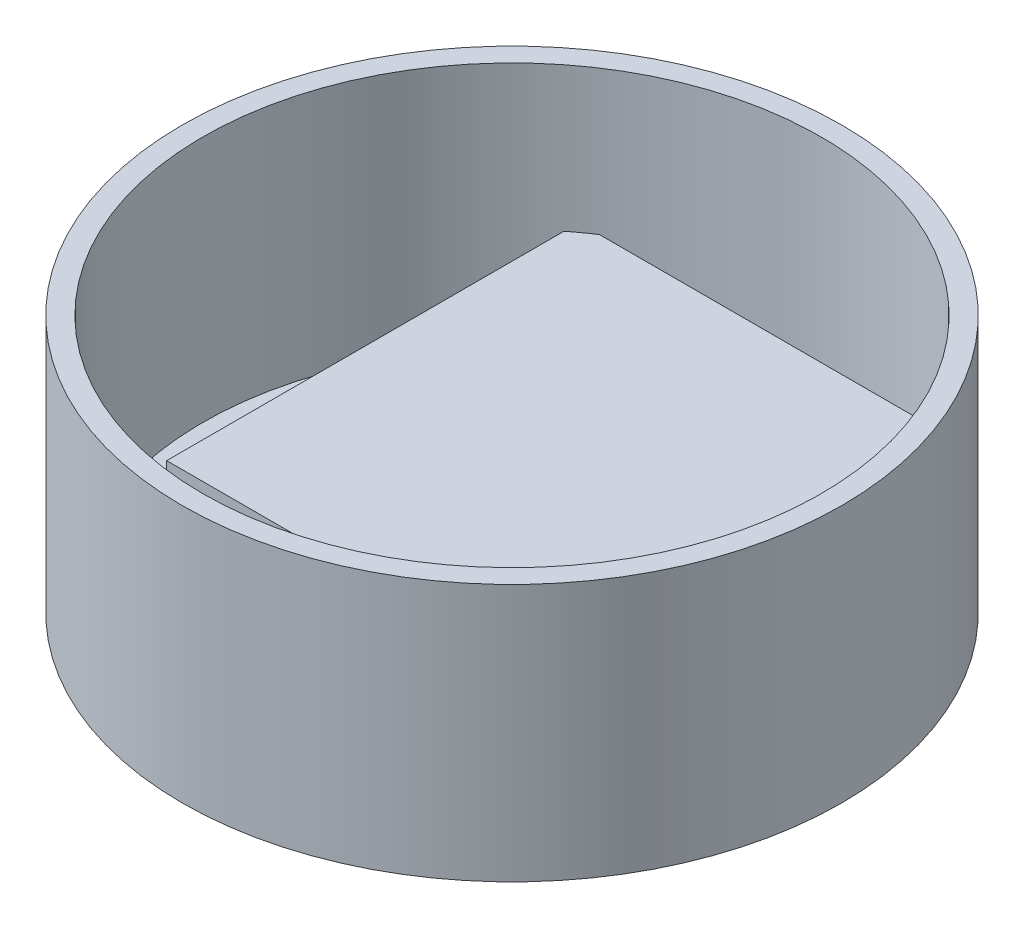
SolidWorks part; units mm, degrees
ref_plane "Front Plane" through (0, 0, 0) normal (0, 0, 1) x (1, 0, 0)
ref_plane "Top Plane" through (0, 0, 0) normal (0, 1, 0) x (1, 0, 0)
ref_plane "Right Plane" through (0, 0, 0) normal (1, 0, 0) x (0, 0, -1)
sketch "Sketch2" plane through (0, 0, 0) normal (0, 1, 0) x (1, 0, 0)
  circle A1 centre (0, 0) radius 32
extrude "Boss-Extrude1" add sketch "Sketch2" along normal blind 25
sketch "Sketch3" plane through (0, 25, 0) normal (0, 1, 0) x (1, 0, 0)
  circle A0 centre (0, 0) radius 30
extrude "Cut-Extrude1" cut sketch "Sketch3" against normal blind 24
sketch "Sketch4" plane through (0, 1, 0) normal (0, 1, 0) x (1, 0, 0)
  line L0 (0, 0) -> (0, 30) construction
  line L4 (-18.5412, -14.9722) -> (18.5412, -14.975)
  line L5 (16.5412, 25.0278) -> (-16.5412, 25.0278)
  line L6 (18.5412, 23.5844) -> (18.5412, -14.975)
  line L9 (-18.5412, -14.9722) -> (-18.5412, 23.5844)
  circle A0 centre (0, 0) radius 30 construction
  arc A1 (16.5412, 25.0278) -> (18.5412, 23.5844) centre (0, 0) cw
  arc A2 (-18.5412, 23.5844) -> (-16.5412, 25.0278) centre (0, 0) cw
extrude "Boss-Extrude2" add sketch "Sketch4" along normal blind 10
